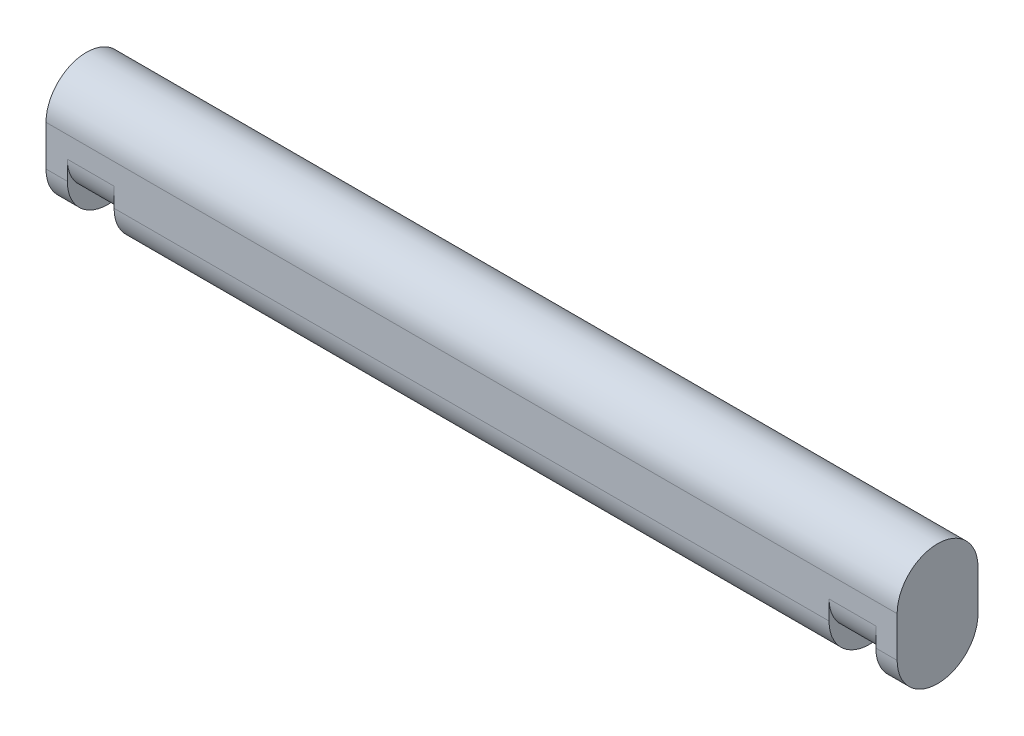
SolidWorks part; units mm, degrees
ref_plane "Front Plane" through (0, 0, 0) normal (0, 0, 1) x (1, 0, 0)
ref_plane "Top Plane" through (0, 0, 0) normal (0, 1, 0) x (1, 0, 0)
ref_plane "Right Plane" through (0, 0, 0) normal (1, 0, 0) x (0, 0, -1)
sketch "Sketch1" plane through (0, 0, 0) normal (1, 0, 0) x (0, 0, -1)
  line L0 (-9.5, 0) -> (-9.5, -9.5)
  line L2 (9.5, -9.5) -> (9.5, 0)
  arc A0 (9.5, 0) -> (-9.5, 0) centre (0, 0) ccw
  arc A1 (-9.5, -9.5) -> (9.5, -9.5) centre (0, -9.5) ccw
  dimension "D1" = 19
extrude "Boss-Extrude1" add sketch "Sketch1" along normal blind 200
sketch "Sketch2" plane through (0, 0, 0) normal (0, 0, 1) x (1, 0, 0)
  line L17 (5, -14) -> (5, -19)
  line L18 (0, -19) -> (200, -19) construction
  line L21 (5, -14) -> (5, -19)
  line L22 (5, -19) -> (16, -19)
  line L23 (16, -14) -> (16, -19)
  line L26 (5, -14) -> (16, -14)
  line L28 (5, -14) -> (16, -14)
  line L29 (5, -14) -> (5, -19)
  line L30 (5, -19) -> (16, -19)
  line L31 (16, -14) -> (16, -19)
  dimension "D1" = 5
  dimension "D2" = 11
extrude "Cut-Extrude1" cut sketch "Sketch2" against normal mid plane 20 contours L23 L17 L22 region at (10.5, -16.5, 0)
fillet "Fillet1" radius 9 2 edges at (10.5, -14, -8.3666) (10.5, -14, 8.3666)
ref_plane "Plane1" through (100, 0, 0) normal (1, 0, 0) x (0, 0, -1)
mirror "Mirror1" about plane through (100, 0, 0) normal (1, 0, 0) of "Fillet1", "Cut-Extrude1"
